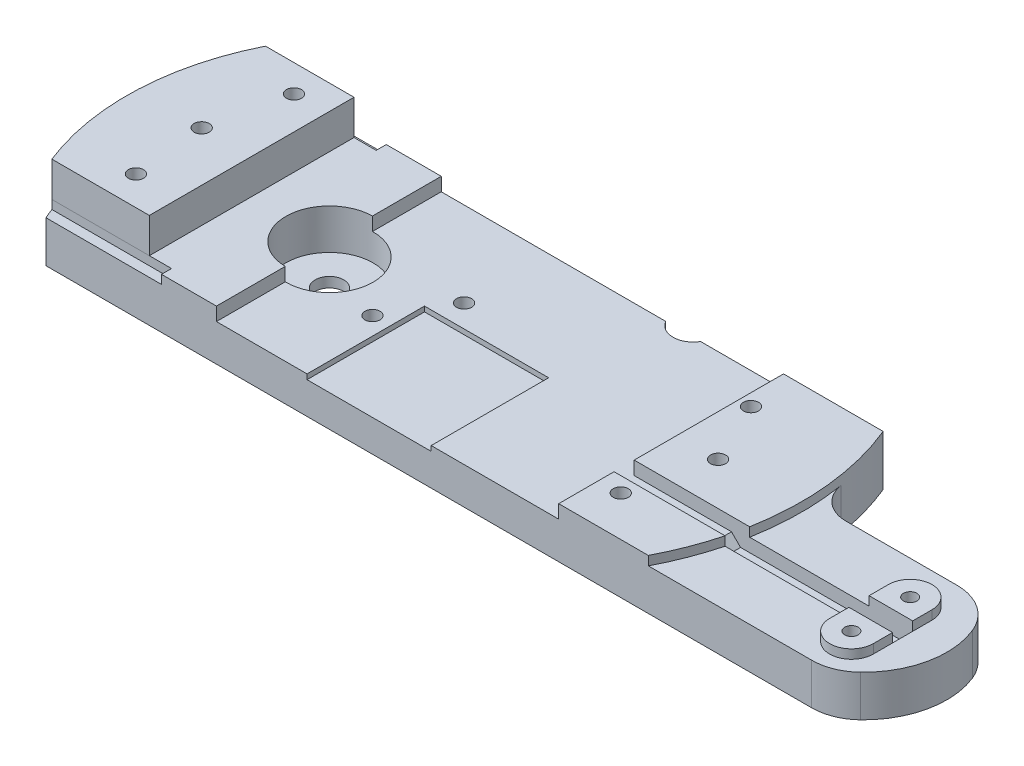
SolidWorks part; units mm, degrees
material "1060 Alloy"
ref_plane "Front Plane" through (0, 0, 0) normal (0, 0, 1) x (1, 0, 0)
ref_plane "Top Plane" through (0, 0, 0) normal (0, 1, 0) x (1, 0, 0)
ref_plane "Right Plane" through (0, 0, 0) normal (1, 0, 0) x (0, 0, -1)
sketch "Sketch1" plane through (0, 0, 0) normal (0, 1, 0) x (1, 0, 0)
  line L1 (-97.5, -33.5) -> (97.5, -33.5)
  line L2 (-97.5, -33.5) -> (-97.5, 33.5)
  line L3 (-97.5, 33.5) -> (97.5, 33.5)
  line L4 (97.5, -33.5) -> (97.5, 33.5)
  line L5 (-97.5, -33.5) -> (97.5, 33.5) construction
  line L6 (-97.5, 33.5) -> (97.5, -33.5) construction
  point P0 (0, 0)
  dimension "D1" = 67
  dimension "D2" = 195
extrude "Boss-Extrude1" add sketch "Sketch1" along normal blind 25.4
sketch "Sketch2" plane through (0, 0, 0) normal (0, -1, 0) x (1, 0, 0)
  line L0 (-97.5, -33.5) -> (-97.5, 33.5) construction
  line L1 (97.5, 33.5) -> (97.5, -33.5) construction
  line L2 (97.5, 33.5) -> (88.5, 33.5)
  line L3 (-97.5, 33.5) -> (97.5, 33.5) construction
  line L4 (97.5, -33.5) -> (91.5, -33.5)
  line L5 (97.5, -33.5) -> (-97.5, -33.5) construction
  line L6 (-97.5, 33.5) -> (-91, 33.5)
  line L7 (-97.5, -33.5) -> (-88, -33.5)
  circle A0 centre (18.0922, -3.2198) radius 79.4078
  circle A1 centre (-22.6589, 2.9929) radius 74.8411
  line M7 (97.5, -33.5) -> (97.5, 33.5)
  line M8 (97.5, 33.5) -> (-97.5, 33.5)
  line M9 (-97.5, 33.5) -> (-97.5, -33.5)
  line M10 (-97.5, -33.5) -> (97.5, -33.5)
  dimension "D1" = 9
  dimension "D2" = 6
  dimension "D3" = 6.5
  dimension "D4" = 9.5
extrude "Cut-Extrude1" cut sketch "Sketch2" against normal through all contours A0 M7 M8 | A0 M10 M7 | A1 M9 M10 | A1 M8 M9 region at (94.8284, 0, 24.4273) region at (95.7123, 0, -25.9883) region at (-95.5654, 0, 25.941) region at (-94.6839, 0, -24.4966)
sketch "Sketch3" plane through (0, 0, 33.5) normal (0, 0, -1) x (-1, 0, 0)
  line L0 (97.5, 25.4) -> (63.2, 25.4)
  line L2 (63.2, 25.4) -> (63.2, 15)
  line L3 (63.2, 15) -> (40.2, 15)
  line L4 (40.2, 15) -> (40.2, 11)
  line L5 (40.2, 11) -> (-61.8, 11)
  line L6 (-91.5, 25.4) -> (88, 25.4) construction
  line L10 (97.5, 0) -> (97.5, 25.4) construction
  line L11 (-61.8, 11) -> (-61.8, 15)
  line L12 (-61.8, 15) -> (-97.5, 15)
  line L13 (-97.5, 25.4) -> (-97.5, 0) construction
  line L14 (-97.5, 15) -> (-97.5, 25.4)
  line L15 (-97.5, 25.4) -> (63.2, 25.4)
  line M13 (-88.5, 0) -> (-88.5, 25.4)
  line M14 (-88.5, 25.4) -> (91, 25.4)
  dimension "D1" = 10.4
  dimension "D2" = 34.3
  dimension "D3" = 23
  dimension "D4" = 4
  dimension "D5" = 102
extrude "Cut-Extrude2" cut sketch "Sketch3" along normal through all contours L11 L12 L2 L3 L4 L5 M13 M14 | L2 L3 L4 L5 L11 L12 L14 L15 region at (12.2699, 18.7206, 33.5)
sketch "Sketch4" plane through (0, 25.4, 0) normal (0, 1, 0) x (1, 0, 0)
  line L0 (-56.5873, 33.5) -> (-56.5873, 30.5)
  line L1 (-63.2, 33.5) -> (-88, 33.5) construction
  line L2 (-56.5873, 30.5) -> (-89.5873, 30.5)
  line L3 (-56.5873, -33.5) -> (-56.5873, -30.5)
  line L4 (-91, -33.5) -> (-63.2, -33.5) construction
  line L5 (-56.5873, -30.5) -> (-92.2617, -30.5)
  line L6 (-56.5873, 33.5) -> (-63.2, 33.5)
  line L7 (-56.5873, -33.5) -> (-63.2, -33.5)
  arc A0 (-88, 33.5) -> (-91, -33.5) centre (-22.6589, -2.9929) ccw construction
  line M5 (-91, -33.5) -> (-63.2, -33.5)
  line M6 (-63.2, -33.5) -> (-63.2, 33.5)
  line M7 (-63.2, 33.5) -> (-88, 33.5)
  arc M8 (-88, 33.5) -> (-91, -33.5) centre (-22.6589, -2.9929) ccw
  dimension "D1" = 3
  dimension "D2" = 3
  dimension "D3" = 33
extrude "Cut-Extrude3" cut sketch "Sketch4" against normal blind 13 contours L2 M6 M7 M8 | L0 L6 L2 M6 | L5 M6 M8 M5 | L7 L3 L5 M6 region at (-59.8937, 25.4, -32) region at (-76.0082, 25.4, -31.9845) region at (-77.4242, 25.4, 31.9889) region at (-59.8937, 25.4, 32)
sketch "Sketch6" plane through (0, 0, 0) normal (0, -1, 0) x (1, 0, 0)
  line L0 (-63.2, -33.5) -> (-97.5, -33.5)
  line L1 (91.5, -33.5) -> (-88, -33.5) construction
  line L2 (-63.2, -33.5) -> (-63.2, 33.5)
  line L3 (-91, 33.5) -> (88.5, 33.5) construction
  line L4 (-63.2, -9) -> (-28.1, -9) construction
  line L5 (-63.2, 8.7) -> (-18.5, 8.7) construction
  line L6 (-63.2, -8.2) -> (-8.1, -8.2) construction
  line L8 (91.5, -33.5) -> (-88, -33.5) construction
  line L9 (-97.5, -33.5) -> (-97.5, 33.5)
  line L10 (-97.5, 33.5) -> (-63.2, 33.5)
  circle A1 centre (-18.5, 8.7) radius 2.25
  circle A2 centre (74.1, -1.7) radius 2.25
  circle A3 centre (68.3, 21.5) radius 2.25
  circle A4 centre (65.4, -20.2) radius 2.25
  circle A5 centre (-8.1, -8.2) radius 2.25
  circle A6 centre (-75.9, 21.8) radius 2.25
  circle A7 centre (-78, 0.1) radius 2.25
  circle A8 centre (-73, -22.4) radius 2.25
  arc A10 (-91, 33.5) -> (-88, -33.5) centre (-22.6589, 2.9929) ccw construction
  dimension "D22" = 4.5
  dimension "D3" = 35.1
  dimension "D4" = 34.3
  dimension "D5" = 44.7
  dimension "D6" = 24.5
  dimension "D7" = 55.1
  dimension "D8" = 42.2
  dimension "D9" = 137.3
  dimension "D10" = 128.6
  dimension "D11" = 131.5
  dimension "D12" = 9.8
  dimension "D13" = 14.8
  dimension "D14" = 12.7
  dimension "D15" = 11.1
  dimension "D16" = 33.6
  dimension "D17" = 55.3
  dimension "D18" = 31.8
  dimension "D19" = 55
  dimension "D20" = 13.3
  dimension "D21" = 25.3
extrude "Cut-Extrude4" cut sketch "Sketch6" against normal through all contours A5 | A1 | A6 | A7 | A8 | A4 | A2 | A3 region at (-18.5, 0, 8.7) region at (74.1, 0, -1.7) region at (68.3, 0, 21.5) region at (65.4, 0, -20.2) region at (-8.1, 0, -8.2) region at (-75.9, 0, 21.8) region at (-78, 0, 0.1) region at (-73, 0, -22.4)
sketch "Sketch7" plane through (0, 11, 0) normal (0, 1, 0) x (1, 0, 0)
  line L1 (-13.2, 1.5) -> (23.8, 1.5)
  line L2 (-13.2, 1.5) -> (-13.2, -33.5)
  line L3 (-13.2, -33.5) -> (23.8, -33.5)
  line L4 (23.8, 1.5) -> (23.8, -33.5)
  line L8 (-63.2, 30.5) -> (-63.2, -30.5) construction
  line L9 (-63.2, 30.5) -> (-63.2, -30.5) construction
  line L10 (-40.2, -33.5) -> (61.8, -33.5) construction
  dimension "D1" = 50
  dimension "D2" = 87
  dimension "D3" = 35
extrude "Cut-Extrude5" cut sketch "Sketch7" against normal blind 1.5
sketch "Sketch8" plane through (0, 25.4, 0) normal (0, 1, 0) x (1, 0, 0)
  line L0 (-56.5873, -33.5) -> (-97.5, -33.5)
  line L1 (-97.5, -33.5) -> (-97.5, 33.5)
  line L3 (-97.5, 33.5) -> (31.9, 33.5)
  line L6 (31.9, 36.5) -> (31.9, 30.5)
  line L7 (31.9, 33.5) -> (37.0962, 33.5)
  line L10 (-56.5873, 33.5) -> (-88, 33.5) construction
  line L11 (-40.2, 33.5) -> (61.8, 33.5) construction
  circle A1 centre (31.9, 36.5) radius 6
  arc A2 (-89.5873, 30.5) -> (-92.2617, -30.5) centre (-22.6589, -2.9929) ccw construction
  dimension "D1" = 12
  dimension "D2" = 129.4
extrude "Cut-Extrude6" cut sketch "Sketch8" against normal blind 18.5 contours L6 A1 L7 | L3 A1 L6 region at (29.8648, 25.4, -32.2699) region at (33.9352, 25.4, -32.2699)
sketch "Sketch9" plane through (0, 0, 0) normal (0, -1, 0) x (1, 0, 0)
  line L0 (88.5, 33.5) -> (137.2004, 33.5)
  line L1 (139.5727, -7.5) -> (97.3846, -7.5)
  arc A0 (153.4738, 1.8643) -> (147.5429, 29.3643) centre (130.3054, 11.2571) ccw
  arc A1 (91.5, -33.5) -> (88.5, 33.5) centre (18.0922, -3.2198) ccw construction
  arc A2 (142.3827, -10.6321) -> (147.5429, 29.3643) centre (130.3054, 11.2571) ccw construction
  arc A3 (147.5429, 29.3643) -> (137.2004, 33.5) centre (137.2004, 18.5) ccw
  arc A4 (147.5429, 29.3643) -> (137.9704, 33.4802) centre (137.2004, 18.5) ccw construction
  arc A5 (139.5727, -7.5) -> (153.4738, 1.8643) centre (139.5727, 7.5) ccw
  circle A6 centre (112.8948, -27.5) radius 16 construction
  circle A7 centre (103.4238, 59.4942) radius 16 construction
  circle A8 centre (112.8948, -27.5) radius 20 construction
  arc A9 (97.3846, -7.5) -> (88.5, 33.5) centre (18.0922, -3.2198) ccw
  circle A10 centre (138.3, 5.25) radius 2
  circle A11 centre (138.3, 22.75) radius 2
  circle A12 centre (138.3, 22.75) radius 2 construction
  circle A13 centre (138.3, 5.25) radius 2 construction
  dimension "D1" = 4
extrude "Boss-Extrude2" add sketch "Sketch9" against normal offset from surface (12.3 mm away) 1.3 up to face at (-16.25, 11, 8.7) offset beyond the face yes
fillet "Fillet1" radius 10 1 edges at (97.3846, 6.15, -7.5)
sketch "Sketch10" plane through (0, 0, 0) normal (0, -1, 0) x (1, 0, 0)
  circle A0 centre (-40.0178, 0) radius 13
  dimension "D1" = 26
extrude "Cut-Extrude7" cut sketch "Sketch10" against normal up to surface (15 mm away) from offset 3 up to face at (-54.1437, 15, 0) offset against normal yes
sketch "Sketch13" plane through (0, 0, 0) normal (0, -1, 0) x (1, 0, 0)
  circle A0 centre (-40.0178, 0) radius 4.25
  dimension "D1" = 8.5
extrude "Cut-Extrude9" cut sketch "Sketch13" against normal through all
sketch "Sketch11" plane through (0, 12.3, 0) normal (0, 1, 0) x (1, 0, 0)
  line L0 (138.3, -5.25) -> (138.3, -22.75) construction
  line L1 (144.8, -5.25) -> (144.8, -22.75)
  line L2 (131.8, -5.25) -> (131.8, -22.75)
  line L3 (131.8, -11) -> (144.8, -11)
  line L4 (131.8, -17) -> (144.8, -17)
  line L5 (131.8, -14) -> (144.8, -14) construction
  arc A0 (144.8, -5.25) -> (131.8, -5.25) centre (138.3, -5.25) ccw
  arc A1 (131.8, -22.75) -> (144.8, -22.75) centre (138.3, -22.75) ccw
  point P4 (138.3, -14)
  circle M15 centre (138.3, -22.75) radius 2
  circle M16 centre (138.3, -5.25) radius 2
  dimension "D1" = 13
  dimension "D2" = 6
extrude "Boss-Extrude3" add sketch "Sketch11" along normal up to surface (2.7 mm away) contours L1 A0 L2 L3 M16 | L2 A1 L1 L4 M15 region at (144.6214, 12.3, 8.125) region at (144.6214, 12.3, 19.875) up to face at (70.55, 15, 21.5)
sketch "Sketch12" plane through (0, 0, 11) normal (0, 0, 1) x (1, 0, 0)
  line L0 (144.8, 15) -> (144.8, 8.3)
  line L1 (144.8, 8.3) -> (93.5, 8.3)
  line L3 (97.5, 12.3) -> (88.5, 12.3) construction
  line L4 (90.8, 11) -> (61.8, 11)
  line L5 (61.8, 11) -> (61.8, 15)
  line L6 (61.8, 15) -> (88.5, 15) construction
  line L7 (61.8, 15) -> (144.8, 15)
  line L10 (97.5, 12.3) -> (93.5, 12.3) construction
  line L12 (88.5, 12.3) -> (137.2004, 12.3) construction
  line L13 (93.5, 12.3) -> (93.5, 8.3) construction
  line L14 (61.8, 11) -> (61.8, 15) construction
  line L15 (23.8, 11) -> (61.8, 11) construction
  line L16 (93.5, 8.3) -> (90.8, 11)
  dimension "D1" = 45
extrude "Cut-Extrude8" cut sketch "Sketch12" along normal up to surface (6 mm away) up to face at (138.3, 13.65, 17)
split "Split1" bodies to split 116 resulting bodies 114 115 split by face at (-52.6367, 15, 0)
